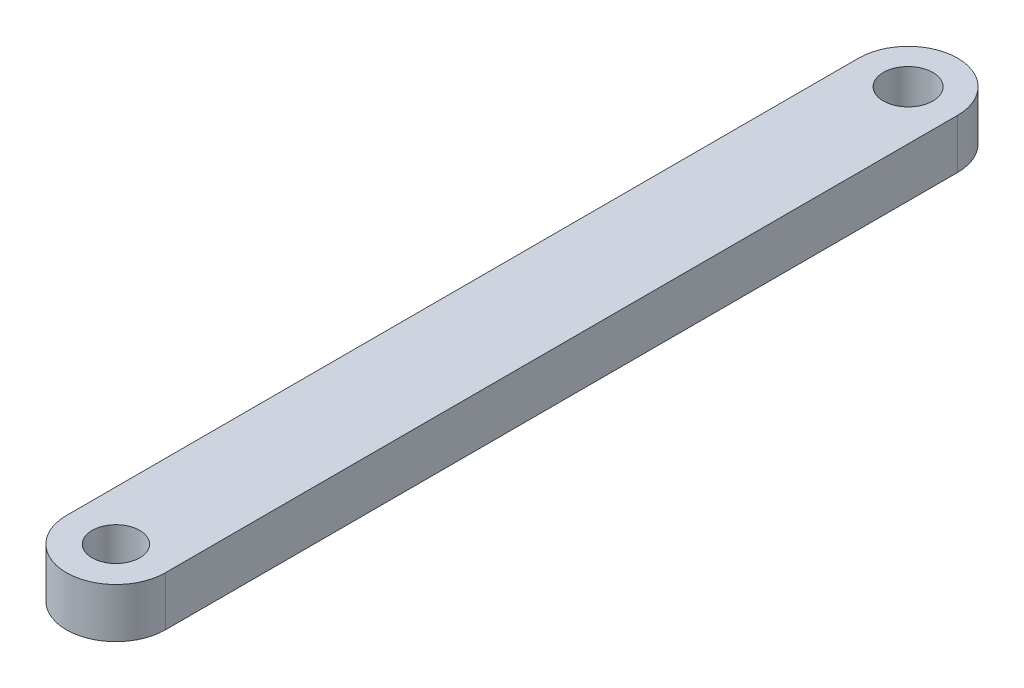
SolidWorks part; units mm, degrees
ref_plane "Front Plane" through (0, 0, 0) normal (0, 0, 1) x (1, 0, 0)
ref_plane "Top Plane" through (0, 0, 0) normal (0, 1, 0) x (1, 0, 0)
ref_plane "Right Plane" through (0, 0, 0) normal (1, 0, 0) x (0, 0, -1)
sketch "Sketch1" plane through (0, 0, 0) normal (0, 1, 0) x (1, 0, 0)
  line L1 (5, 0) -> (-5, 0)
  line L2 (5, 0) -> (5, 80)
  line L3 (-5, 0) -> (-5, 80)
  line L4 (5, 80) -> (-5, 80)
  circle A1 centre (0, 0) radius 5
  circle A2 centre (0, 80) radius 5
  circle A3 centre (0, 0) radius 2.4046
  circle A4 centre (0, 80) radius 2.5
  dimension "D1" = 80
  dimension "D2" = 10
  dimension "D3" = 5
extrude "Boss-Extrude3" add sketch "Sketch1" along normal blind 5 contours A3 L1 A1 | A3 L1 A1 | A2 L3 A1 L2 | A4 L4 A2 | A4 L4 A2 region at (0, 0, 2.4535) region at (0, 0, -40) region at (0, 0, -2.4535) region at (0, 0, -75.1118) region at (3.75, 0, -80.1118)
ref_axis "Axis2" through (0, 5, -80) along (0, -1, 0)
ref_axis "Axis1" through (0, 5, 0) along (0, -1, 0)
equation "\"Shaft_Diameter\"= 5mm"
